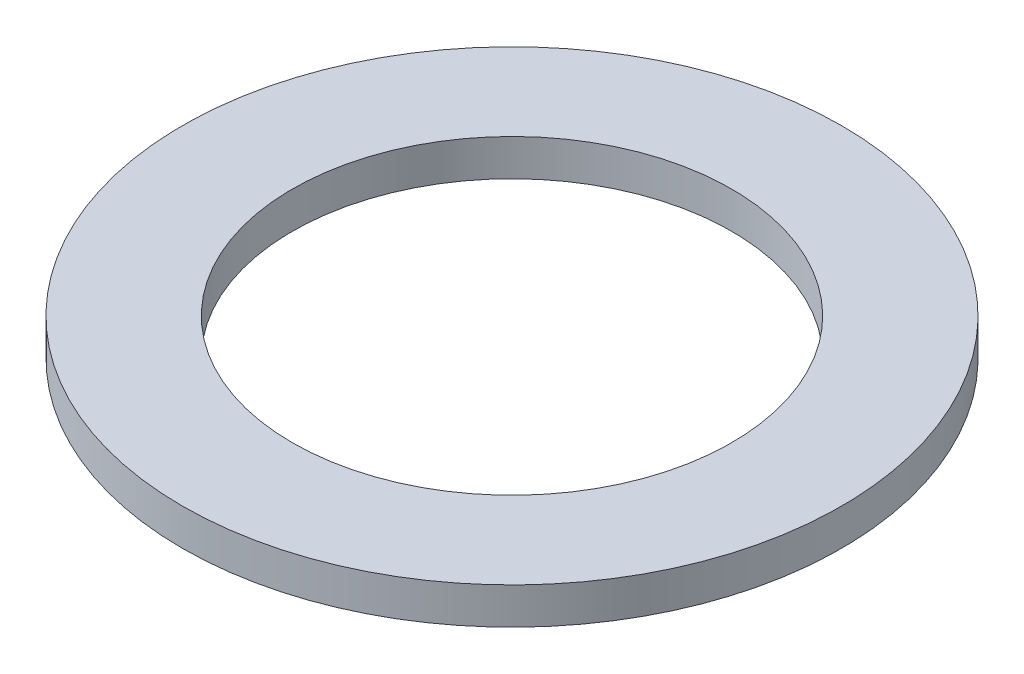
SolidWorks part; units mm, degrees
ref_plane "Front Plane" through (0, 0, 0) normal (0, 0, 1) x (1, 0, 0)
ref_plane "Top Plane" through (0, 0, 0) normal (0, 1, 0) x (1, 0, 0)
ref_plane "Right Plane" through (0, 0, 0) normal (1, 0, 0) x (0, 0, -1)
sketch "Sketch1" plane through (0, 0, 0) normal (0, 1, 0) x (1, 0, 0)
  circle A0 centre (0, 0) radius 45
  dimension "FLANGE_OD" = 90
extrude "Boss-Extrude1" add sketch "Sketch1" along normal blind 5
sketch "Sketch2" plane through (0, 0, 0) normal (0, 1, 0) x (1, 0, 0)
  circle A0 centre (0, 0) radius 30
  dimension "BORE_D" = 60
extrude "Cut-Extrude1" cut sketch "Sketch2" along normal through all
sketch "Sketch3" plane through (0, 5, 0) normal (0, 1, 0) x (1, 0, 0)
  circle A0 centre (0, 0) radius 17.6583 construction
  circle A1 centre (-17.6583, 0) radius 1.7656
  dimension "BOLT_D" = 3.5313
  dimension "BOLT_PCD" = 35.3166
extrude "Cut-Extrude2" cut sketch "Sketch3" against normal blind 4.5494 rebuild error yes
pattern_circular "CirPattern1" count 8 over 360 rebuild error yes
